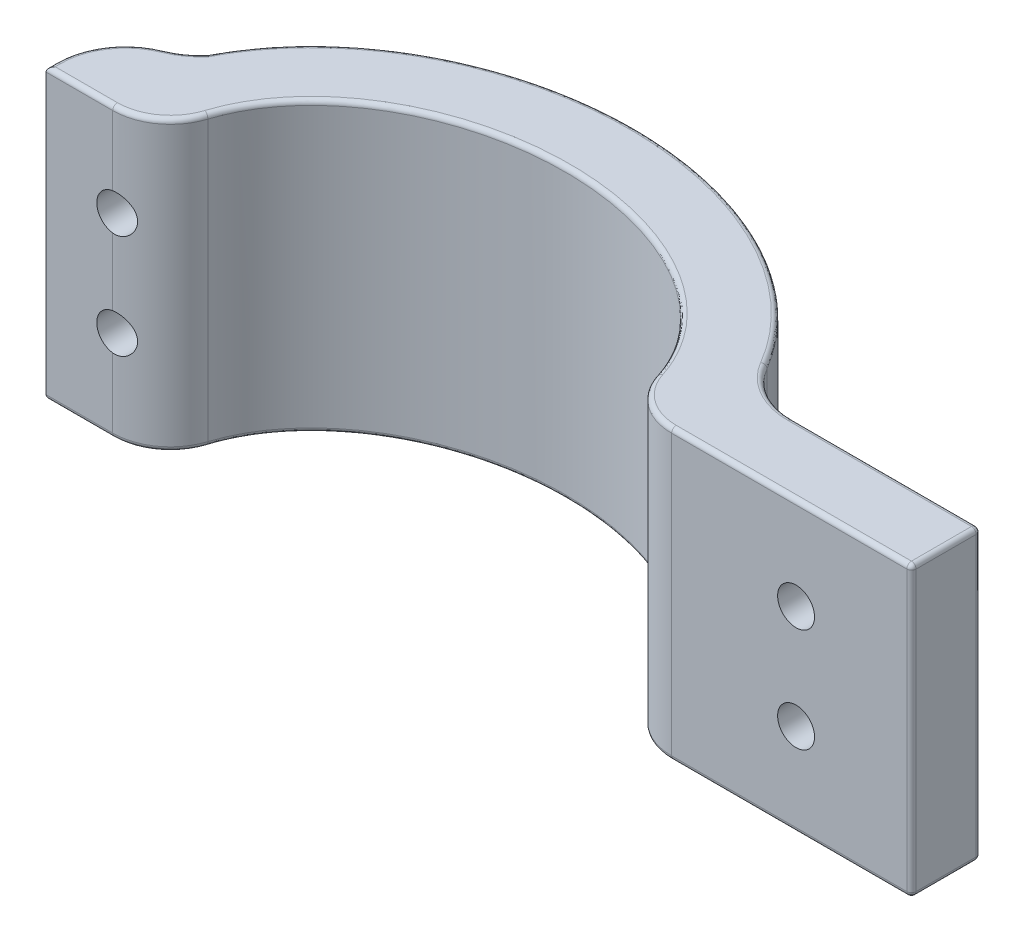
SolidWorks part; units mm, degrees
ref_plane "Front Plane" through (0, 0, 0) normal (0, 0, 1) x (1, 0, 0)
ref_plane "Top Plane" through (0, 0, 0) normal (0, 1, 0) x (1, 0, 0)
ref_plane "Right Plane" through (0, 0, 0) normal (1, 0, 0) x (0, 0, -1)
sketch "Sketch1" plane through (0, 0, 0) normal (0, 1, 0) x (1, 0, 0)
  line L0 (-30, 6) -> (-24.6393, 6)
  line L5 (-30, 0) -> (-20, 0)
  line L6 (-30, 6) -> (-30, 0)
  line L7 (45, 6) -> (45, 0)
  line L8 (20, 0) -> (45, 0)
  line L9 (24.9162, 6) -> (45, 6)
  line L10 (-24.6393, 6) -> (-24.0395, 8)
  ellipse E0 centre (0, 0) end of major axis (20, 0) minor radius 15 (20, 0) -> (-20, 0) ccw
  ellipse E1 centre (0, 0) end of major axis (-26, 0) minor radius 21 (24.9162, 6) -> (-24.0395, 8) ccw
  dimension "D1" = 40
  dimension "D2" = 30
  dimension "D4" = 6
  dimension "D3" = 10
  dimension "D5" = 25
  dimension "D6" = 52
  dimension "D7" = 42
  dimension "D8" = 6
extrude "Boss-Extrude2" add sketch "Sketch1" along normal blind 25
fillet "圆角2" radius 6 2 edges at (-24.6393, 12.5, -6) (24.9162, 12.5, -6)
fillet "圆角3" radius 6 1 edges at (-30, 12.5, -6)
sketch "草图2" plane through (0, 0, 0) normal (0, 0, 1) x (1, 0, 0)
  line L0 (-30, 25) -> (-20, 25) construction
  line L1 (-30, 0) -> (-20, 0) construction
  line L2 (-30, 25) -> (-30, 0) construction
  line L3 (20, 25) -> (45, 25) construction
  line L4 (20, 0) -> (45, 0) construction
  line L5 (45, 25) -> (45, 0) construction
  circle A0 centre (-24, 17) radius 1.6
  circle A1 centre (-24, 8) radius 1.6
  circle A2 centre (35, 17) radius 1.6
  circle A3 centre (35, 8) radius 1.6
  dimension "D1" = 3.2
  dimension "3.2" = 3.2
  dimension "D2" = 3.2
  dimension "D3" = 3.2
  dimension "D7" = 6
  dimension "D9" = 8
  dimension "D10" = 10
  dimension "D11" = 10
  dimension "D4" = 8
  dimension "D5" = 8
  dimension "D6" = 6
  dimension "D8" = 8
extrude "切除-拉伸1" cut sketch "草图2" against normal through all
ref_plane "基准面1" through (0, 0, -20) normal (0, 0, 1) x (1, 0, 0)
sketch "草图3" plane through (0, 0, -20) normal (0, 0, 1) x (1, 0, 0)
  circle A0 centre (-24, 17) radius 2.75
  circle A1 centre (-24, 8) radius 2.75
  dimension "D1" = 5.5
  dimension "D2" = 5.5
extrude "切除-拉伸2" cut sketch "草图3" along normal blind 15
fillet "圆角4" radius 5 2 edges at (-20, 12.5, 0) (20, 12.5, 0)
fillet "圆角5" radius 0.4 24 edges at (21.2667, 0, -0.9637) (34.6088, 0, 0) (45, 0, -3) (36.8438, 0, -6) (25.7022, 0, -6.7954) (-0.6569, 0, -20.9933) (-25.0584, 0, -7.0933) (-28.9767, 0, -4.2319) (-30, 0, -0.4402) (-27.1088, 0, 0) (-21.2667, 0, -0.9637) (0, 0, -15) (-30, 25, -0.4402) (-28.9767, 25, -4.2319) (-25.0584, 25, -7.0933) (-0.6569, 25, -20.9933) (25.7022, 25, -6.7954) (36.8438, 25, -6) (45, 25, -3) (34.6088, 25, 0) (21.2667, 25, -0.9637) (0, 25, -15) (-21.2667, 25, -0.9637) (-27.1088, 25, 0)
fillet "圆角6" radius 0.4 6 edges at (44.8828, 24.8828, -0.1172) (44.8828, 0.1172, -0.1172) (45, 12.5, 0) (44.8828, 24.8828, -5.8828) (44.8828, 0.1172, -5.8828) (45, 12.5, -6)
